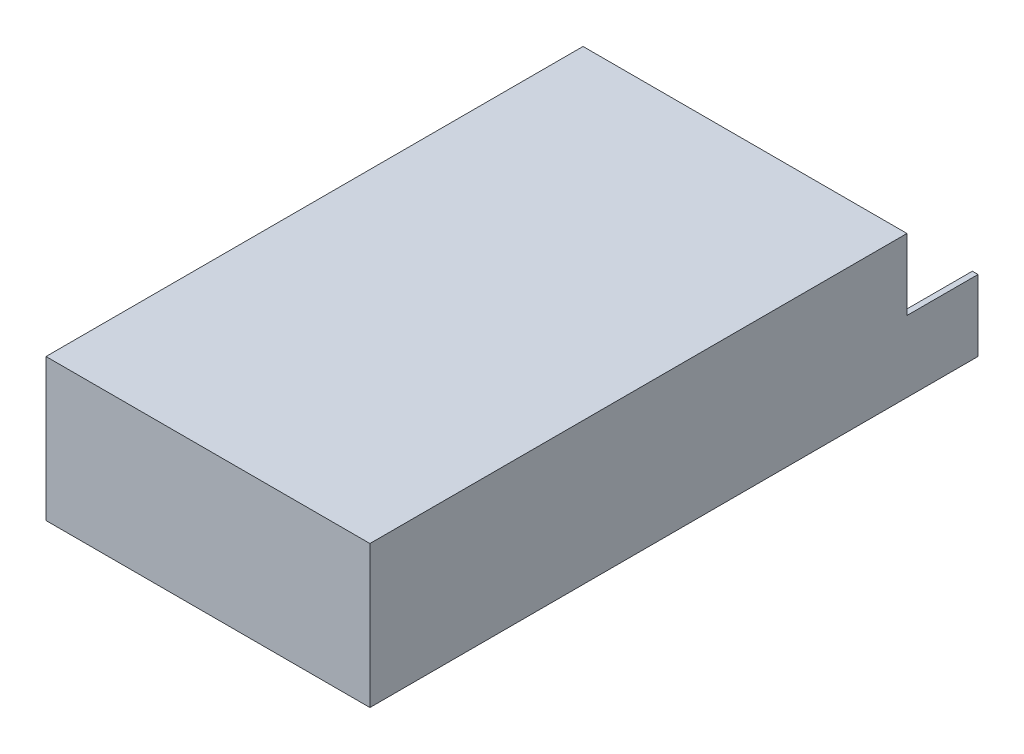
SolidWorks part; units mm, degrees
ref_plane "Front" through (0, 0, 0) normal (0, 0, 1) x (1, 0, 0)
ref_plane "Top" through (0, 0, 0) normal (0, 1, 0) x (1, 0, 0)
ref_plane "Right" through (0, 0, 0) normal (1, 0, 0) x (0, 0, -1)
sketch "Sketch1" plane through (0, 0, 0) normal (0, 1, 0) x (1, 0, 0)
  line L1 (0, 0) -> (114, 0)
  line L2 (0, 0) -> (0, 214)
  line L3 (0, 214) -> (114, 214)
  line L4 (114, 0) -> (114, 214)
  dimension "D1" = 114
  dimension "D2" = 214
extrude "Boss-Extrude1" add sketch "Sketch1" along normal blind 50
sketch "Sketch4" plane through (114, 0, 0) normal (1, 0, 0) x (0, 0, -1)
  line L0 (0, 0) -> (214, 0) construction
  line L1 (214, 50) -> (189, 50)
  line L2 (214, 50) -> (214, 25)
  line L3 (214, 25) -> (189, 25)
  line L4 (189, 50) -> (189, 25)
  dimension "D1" = 25
  dimension "D2" = 25
extrude "Cut-Extrude1" cut sketch "Sketch4" against normal through all
shell "Shell1" thickness 2 removed face at (57, 12.5, -214) removed face at (57, 25, -201.5)
hole_wizard "M4 Clearance Hole1" positions "Sketch2" profile "Sketch3" hole size "M4" standard "ANSI Metric"
sketch "Sketch2" plane through (0, 0, 0) normal (0, -1, 0) x (-1, 0, 0)
  line L9 (-57, 214) -> (-57, 0) construction
  line L10 (-114, 214) -> (0, 214) construction
  line L11 (0, 0) -> (-114, 0) construction
  line L15 (-82, 32) -> (-32, 32)
  line L16 (-82, 32) -> (-82, 182)
  line L17 (-82, 182) -> (-32, 182)
  line L18 (-32, 32) -> (-32, 182)
  line L19 (-82, 32) -> (-32, 182) construction
  line L20 (-82, 182) -> (-32, 32) construction
  point P80 (-57, 107)
  point P81 (-32, 182)
  point P84 (-82, 32)
  point P85 (-82, 182)
  point P86 (-32, 32)
  dimension "D1" = 50
  dimension "D2" = 150
sketch "Sketch3" plane through (32, 0, -32) normal (1, 0, 0) x (0, 0, -1)
  line L0 (0, 0) -> (0, 5.2919)
  line L1 (0, 5.2919) -> (2.15, 4)
  line L2 (2.15, 4) -> (2.15, 0)
  line L5 (2.15, 0) -> (0, 0)
  line L10 (0, 5.2919) -> (-2.15, 4) construction
  line L11 (0, -6.35) -> (0, 107.95) construction
  dimension "Hole Dia." = 4.3
  dimension "Hole Depth" = 4
  dimension "Drill Angle" = 118
